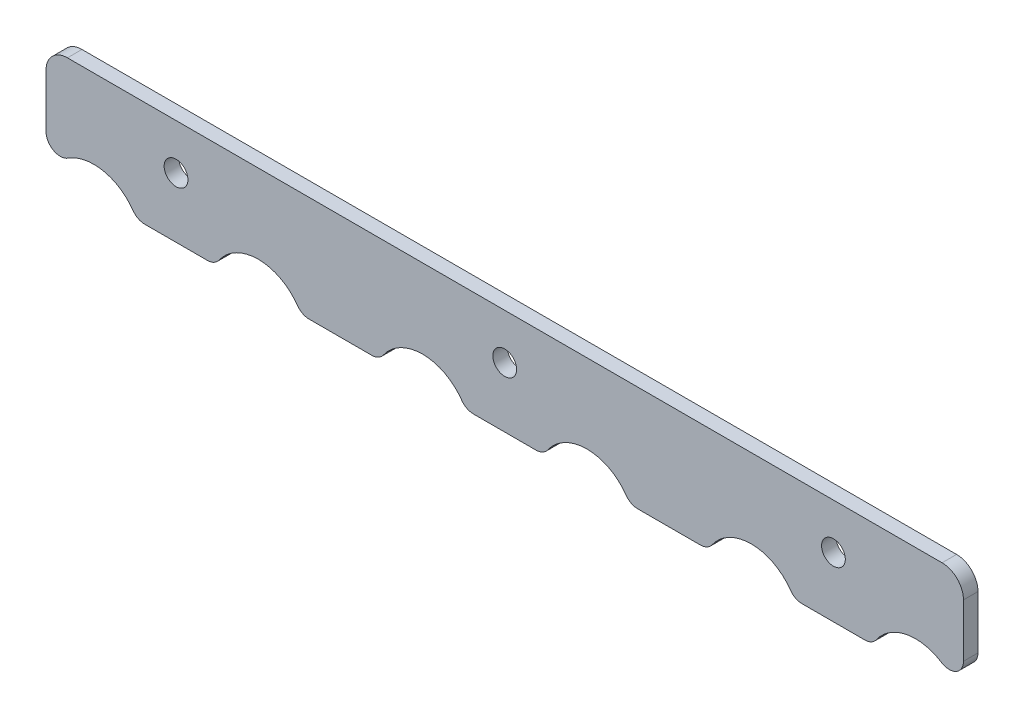
SolidWorks part; units mm, degrees
material "3003-H14"
ref_plane "X-Y Datum" through (0, 0, 0) normal (0, 0, 1) x (1, 0, 0)
ref_plane "X-Z Datum" through (0, 0, 0) normal (0, 1, 0) x (1, 0, 0)
ref_plane "Y-Z Datum" through (0, 0, 0) normal (1, 0, 0) x (0, 0, -1)
sketch "Sketch3" plane through (0, 0, 0) normal (0, 0, 1) x (1, 0, 0)
  line L1 (0, 0) -> (156.4633, 0) construction
  line L2 (0, 0) -> (0, 56.3098) construction
  line L3 (0, 56.3098) -> (156.4633, 56.3098) construction
  line L4 (156.4633, 0) -> (156.4633, 56.3098) construction
  line L5 (4.075, 10.775) -> (4.075, 28.535)
  line L6 (4.075, 28.535) -> (132.475, 28.535)
  line L7 (132.475, 28.535) -> (132.475, 10.775)
  line L9 (4.075, 13.775) -> (132.475, 13.775)
  line L10 (10.775, 10.775) -> (33.775, 10.775) construction
  line L11 (56.775, 10.775) -> (33.775, 10.775) construction
  line L48 (56.775, 10.775) -> (125.775, 10.775) construction
  circle A0 centre (10.775, 10.775) radius 10.775 construction
  circle A1 centre (33.775, 10.775) radius 10.775 construction
  circle A5 centre (56.775, 10.775) radius 10.775 construction
  circle A6 centre (10.775, 10.775) radius 4.7 construction
  circle A7 centre (33.775, 10.775) radius 4.7 construction
  circle A8 centre (56.775, 10.775) radius 4.7 construction
  circle A12 centre (79.775, 10.775) radius 10.775 construction
  circle A13 centre (79.775, 10.775) radius 4.7 construction
  circle A14 centre (102.775, 10.775) radius 10.775 construction
  circle A15 centre (102.775, 10.775) radius 4.7 construction
  circle A16 centre (125.775, 10.775) radius 10.775 construction
  circle A17 centre (125.775, 10.775) radius 4.7 construction
  circle A18 centre (125.775, 10.775) radius 10.775 construction
  circle A19 centre (102.775, 10.775) radius 10.775 construction
  circle A20 centre (79.775, 10.775) radius 10.775 construction
  circle A25 centre (10.775, 10.775) radius 6.7
  circle A26 centre (33.775, 10.775) radius 6.7
  circle A27 centre (56.775, 10.775) radius 6.7
  circle A28 centre (79.775, 10.775) radius 6.7
  circle A29 centre (102.775, 10.775) radius 6.7
  circle A30 centre (125.775, 10.775) radius 6.7
  dimension "D1" = 21.55
  dimension "D9" = 9.4
  dimension "D2" = 23
  dimension "D3" = 2
  dimension "D4" = 14.76
  dimension "D8" = 23
  dimension "D11" = 23
  dimension "D5" = 3
  dimension "D10" = 4
  dimension "D7" = 5
extrude "Boss-Extrude1" add sketch "Sketch3" along normal blind 2.032 contours A30 L9 L7 L6 L5 A25 A26 A27 A28 A29 | A25 L9 L5 | A30 L7 L9 region at (4.2857, 13.0332, 0) region at (68.275, 21.8085, 0) region at (132.2643, 13.0332, 0)
fillet "Fillet1" radius 3 2 edges at (4.075, 28.535, 1.016) (132.475, 28.535, 1.016)
fillet "Fillet2" radius 2 12 edges at (132.475, 10.775, 1.016) (119.7842, 13.775, 1.016) (108.7658, 13.775, 1.016) (96.7842, 13.775, 1.016) (85.7658, 13.775, 1.016) (73.7842, 13.775, 1.016) (62.7658, 13.775, 1.016) (50.7842, 13.775, 1.016) (39.7658, 13.775, 1.016) (27.7842, 13.775, 1.016) (16.7658, 13.775, 1.016) (4.075, 10.775, 1.016)
sketch "Sketch4" plane through (0, 0, 0) normal (0, 0, -1) x (-1, 0, 0)
  line L0 (-132.475, 22.185) -> (-4.075, 22.185) construction
  line L1 (-132.475, 25.535) -> (-132.475, 18.0962) construction
  line L2 (-4.075, 18.0962) -> (-4.075, 25.535) construction
  line L3 (-7.075, 28.535) -> (-129.475, 28.535) construction
  line L4 (-68.275, 28.535) -> (-68.275, 13.775) construction
  line L5 (-63.8947, 13.775) -> (-72.6553, 13.775) construction
  line L6 (-68.275, 22.185) -> (-4.075, 22.185) construction
  line L7 (-22.275, 13.775) -> (-22.275, 28.535) construction
  line L8 (-17.8947, 13.775) -> (-26.6553, 13.775) construction
  line L9 (-114.275, 13.775) -> (-114.275, 28.535) construction
  line L10 (-109.8947, 13.775) -> (-118.6553, 13.775) construction
  circle A0 centre (-22.275, 22.185) radius 1.6637
  circle A1 centre (-68.275, 22.185) radius 1.6637
  circle A3 centre (-114.275, 22.185) radius 1.6637
  point P30 (-68.275, 22.185)
  dimension "D1" = 3.3274
  dimension "D2" = 6.35
extrude "Cut-Extrude1" cut sketch "Sketch4" against normal through all
